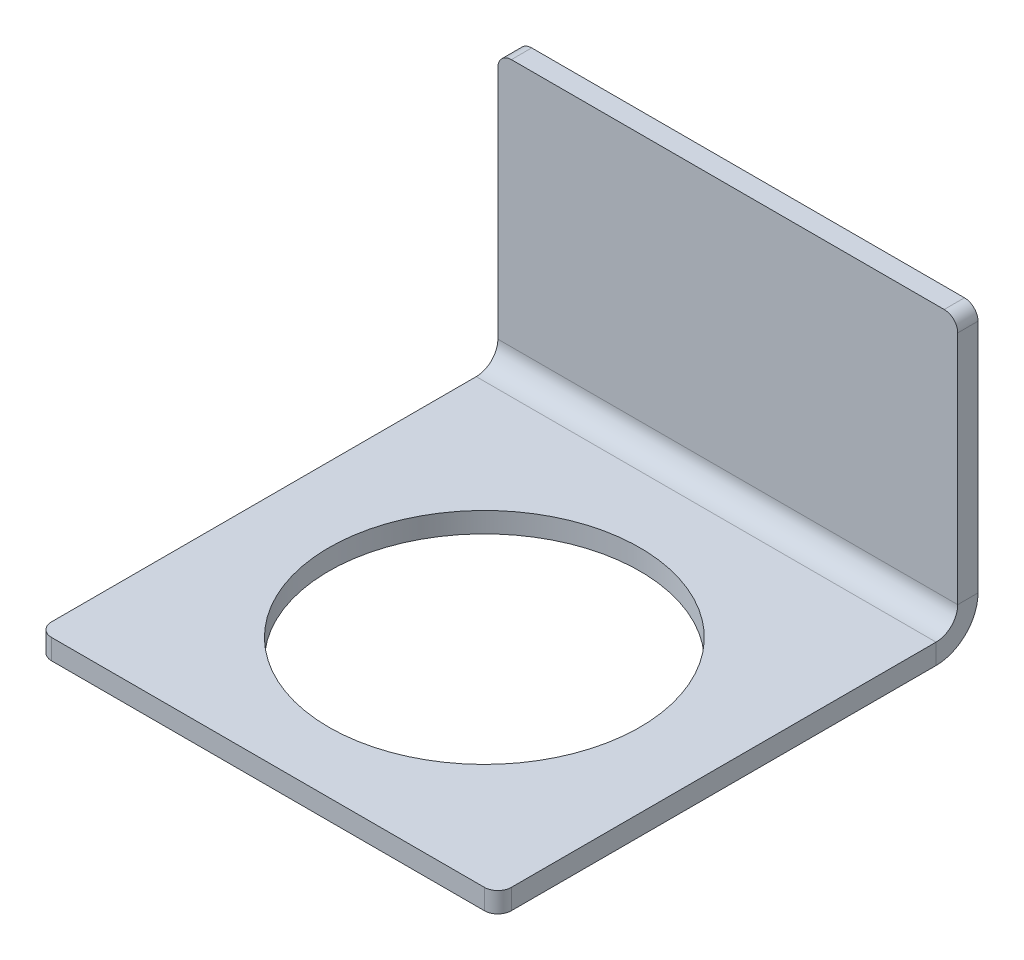
SolidWorks part; units mm, degrees
note: The reader was unsure of these and kept them because the rebuilt part matched: bend radius of "Основание1".
material "AISI 304"
ref_plane "Спереди" through (0, 0, 0) normal (0, 0, 1) x (1, 0, 0)
ref_plane "Сверху" through (0, 0, 0) normal (0, 1, 0) x (1, 0, 0)
ref_plane "Справа" through (0, 0, 0) normal (1, 0, 0) x (0, 0, -1)
sketch "Эскиз1" plane through (0, 0, 0) normal (1, 0, 0) x (0, 0, -1)
  line L0 (-34, 0) -> (0, 0)
  line L1 (0, 0) -> (0, 20)
  dimension "D1" = 34
  dimension "D2" = 20
base flange "Базовая кромка1" sketch "Эскиз1" end condition mid plane depth 34 reverse direction no thickness 1.5 reverse thickness direction no bend radius 1.6
bend "Основание1" bend radius 1.6 bend angle 90 parameters "D5"=1
sketch "Эскиз6" plane through (0, 0, 0) normal (0, 1, 0) x (1, 0, 0)
  line L0 (17, -34) -> (-17, -34) construction
  circle A0 centre (0, -18) radius 11.5
  point P4 (0, 0)
  dimension "D1" = 23
  dimension "D2" = 16
extrude "Вырез-Вытянуть1" cut sketch "Эскиз6" against normal through all normal cut yes
fillet "Скругление1" radius 1 4 edges at (-17, 20, -0.75) (17, 20, -0.75) (17, -0.75, 34) (-17, -0.75, 34)
sketch "Сгиб-Линии1" [suppressed] plane through (0, 0, 0) normal (0, 1, 0) x (1, 0, 0)
sketch "Граничная рамка1" [suppressed] plane through (0, 0, 0) normal (0, 1, 0) x (1, 0, 0)
sheet metal parameters "Листовой металл3" thickness 1.5 parameters "D1"=1.6
flat pattern "Развертка3" [suppressed]
sketch "Сгиб-Линии2" plane through (0, 0, 0) normal (0, 1, 0) x (1, 0, 0)
sketch "Граничная рамка2" [suppressed] plane through (0, 0, 0) normal (0, 1, 0) x (1, 0, 0)
bend of the flat pattern "Плоское состояние-<Основание1>1"
sheet metal parameters "Листовой металл4" thickness 1.5 parameters "D1"=1.6
flat pattern "Развертка3"
sketch "Сгиб-Линии2" plane through (0, 0, 0) normal (0, 1, 0) x (1, 0, 0)
  line L0 (-17, 0.1043) -> (17, 0.1043) construction
  line L1 (-17, 0.1043) -> (17, 0.1043) construction
sketch3d "Граничная рамка2" [suppressed]
  line L0 (-34, 54.2086, 0) -> (-34, 0, 0) construction
  line L1 (0, 54.2086, 0) -> (0, 0, 0) construction
  line L2 (-34, 54.2086, 0) -> (0, 54.2086, 0) construction
  line L3 (-34, 0, 0) -> (0, 0, 0) construction
bend of the flat pattern "Плоское состояние-<Основание1>1"
